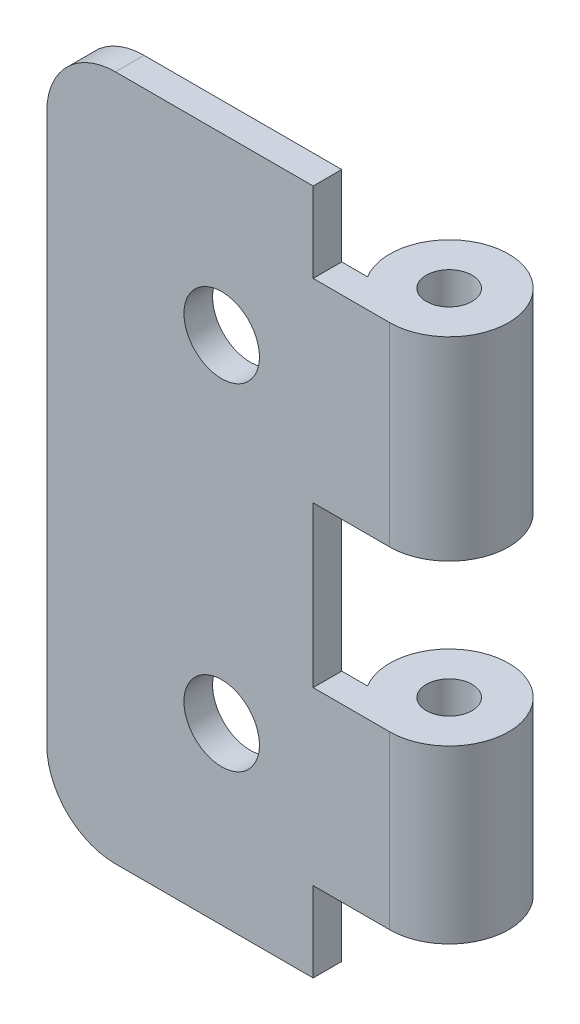
SolidWorks part; units mm, degrees
ref_plane "Front Plane" through (0, 0, 0) normal (0, 0, 1) x (1, 0, 0)
ref_plane "Top Plane" through (0, 0, 0) normal (0, 1, 0) x (1, 0, 0)
ref_plane "Right Plane" through (0, 0, 0) normal (1, 0, 0) x (0, 0, -1)
sketch "Sketch1" plane through (0, 0, 0) normal (0, 1, 0) x (1, 0, 0)
  line L0 (29.591, 3.175) -> (32.456, 3.175)
  line L1 (0, 0) -> (29.591, 0)
  line L2 (0, 0) -> (0, 3.175)
  line L3 (0, 3.175) -> (29.591, 3.175)
  line L4 (29.591, 0) -> (29.591, 3.175)
  line L5 (29.591, 0) -> (38.1, 0)
  circle A0 centre (38.1, 6.604) radius 6.604
  dimension "D3" = 13.208
  dimension "D1" = 3.175
  dimension "D2" = 29.591
  dimension "D4" = 38.1
extrude "Boss-Extrude1" add sketch "Sketch1" along normal blind 76.2 contours L1 L4 L3 L2 | A0 L0 L4 L5 | A0 region at (14.7955, 0, -1.5875) region at (32.0358, 0, -1.3339) region at (38.1, 0, -6.604)
sketch "Sketch2" plane through (0, 0, -3.175) normal (0, 0, -1) x (-1, 0, 0)
  line L0 (0, 76.2) -> (-32.456, 76.2) construction
  line L1 (0, 76.2) -> (0, 0) construction
  line L2 (0, 0) -> (-32.456, 0) construction
  circle A0 centre (-19.431, 56.769) radius 4.191
  circle A1 centre (-19.431, 19.431) radius 4.191
  dimension "D1" = 8.382
  dimension "D4" = 8.382
  dimension "D2" = 19.431
  dimension "D3" = 19.431
  dimension "D5" = 19.431
  dimension "D6" = 19.431
extrude "Cut-Extrude1" cut sketch "Sketch2" against normal blind 50.8
extrude "Cut-Extrude2" cut sketch "Sketch1<3>" along normal blind 8.89 contours A0 L0 L4 L5 | A0 region at (32.0358, 0, -1.3339) region at (38.1, 0, -6.604)
sketch "Sketch1<3>" plane through (0, 0, 0) normal (0, 1, 0) x (1, 0, 0) same geometry as "Sketch1"
extrude "Cut-Extrude3" cut sketch "Sketch1<5>" along normal blind 17.78 from offset 27.94 contours A0 | A0 L0 L4 L5 region at (32.0358, 0, -1.3339) region at (38.1, 0, -6.604)
sketch "Sketch1<5>" plane through (0, 0, 0) normal (0, 1, 0) x (1, 0, 0) same geometry as "Sketch1"
sketch "Sketch3" plane through (0, 76.2, 0) normal (0, 1, 0) x (1, 0, 0)
  arc A0 (38.1, 0) -> (32.456, 3.175) centre (38.1, 6.604) ccw construction
  arc A1 (38.1, 0) -> (32.456, 3.175) centre (38.1, 6.604) ccw
  circle A2 centre (38.1, 6.604) radius 2.54
  dimension "D1" = 5.08
extrude "Cut-Extrude4" cut sketch "Sketch3" against normal through all contours A2 region at (38.1, 76.2, -6.604)
extrude "Cut-Extrude5" cut sketch "Sketch1<6>" against normal blind 8.89 from offset 76.2 contours A0 | A0 L0 L4 L5 region at (32.0358, 0, -1.3339) region at (38.1, 0, -6.604)
sketch "Sketch1<6>" plane through (0, 0, 0) normal (0, 1, 0) x (1, 0, 0) same geometry as "Sketch1"
fillet "Fillet1" radius 7.62 1 edges at (0, 0, -1.5875) type face fillet first side face at (0, 38.1, -1.5875) second side face at (14.7955, 0, -1.5875)
fillet "Fillet2" radius 7.62 1 edges at (0, 76.2, -1.5875) type face fillet first side face at (14.7955, 76.2, -1.5875) second side face at (0, 41.91, -1.5875)
